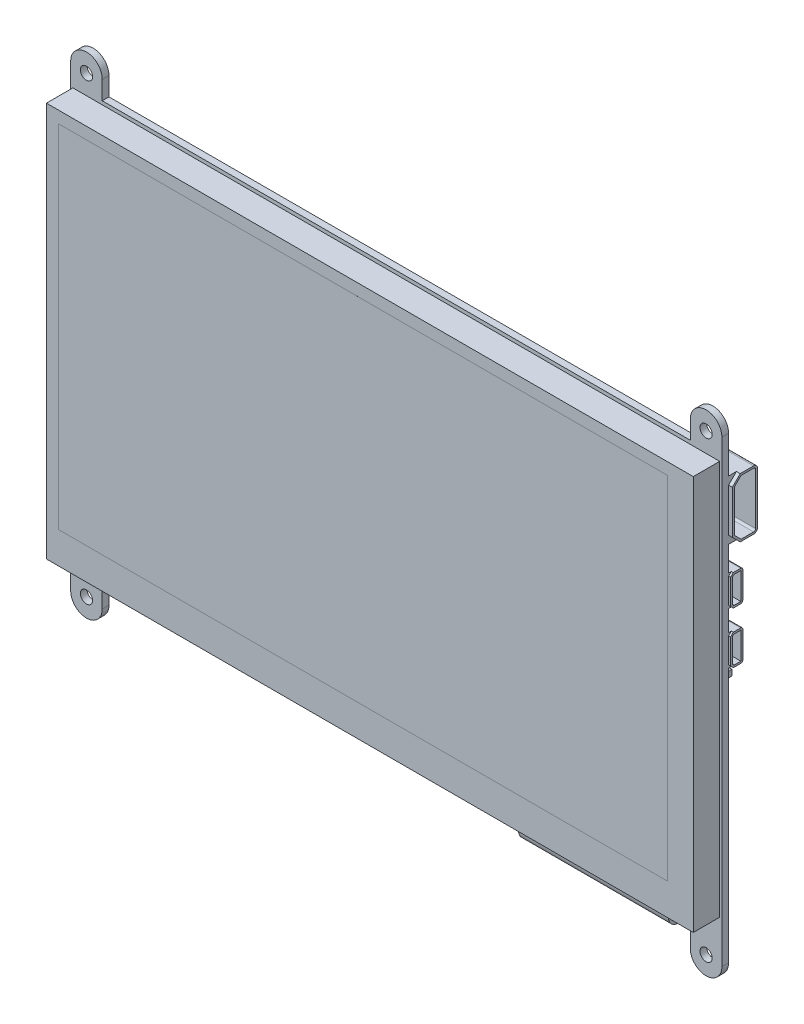
SolidWorks part; units mm, degrees
ref_plane "Přední rovina" through (0, 0, 0) normal (0, 0, 1) x (1, 0, 0)
ref_plane "Horní rovina" through (0, 0, 0) normal (0, 1, 0) x (1, 0, 0)
ref_plane "Pravá rovina" through (0, 0, 0) normal (1, 0, 0) x (0, 0, -1)
sketch "Skica1" plane through (0, 0, 0) normal (0, 0, 1) x (1, 0, 0)
  line L1 (-82, -50.05) -> (82, -50.05)
  line L2 (-82, -50.05) -> (-82, 50.05)
  line L3 (-82, 50.05) -> (82, 50.05)
  line L4 (82, -50.05) -> (82, 50.05)
  line L5 (-82, -50.05) -> (82, 50.05) construction
  line L6 (-82, 50.05) -> (82, -50.05) construction
  line L7 (-82.55, -55.95) -> (82.55, -55.95)
  line L8 (-82.55, -55.95) -> (-82.55, 50.95)
  line L9 (-82.55, 50.95) -> (82.55, 50.95)
  line L10 (82.55, -55.95) -> (82.55, 50.95)
  line L11 (-82.55, -55.95) -> (82.55, 50.95) construction
  line L12 (-82.55, 50.95) -> (82.55, -55.95) construction
  point P0 (0, 0)
  point P6 (0, -2.5)
  dimension "D1" = 100.1
  dimension "D2" = 164
  dimension "D3" = 106.9
  dimension "D4" = 0.55
  dimension "D5" = 0.55
  dimension "D6" = 0.9
extrude "Přidat vysunutím1" add sketch "Skica1" along normal blind 6.7 contours L1 L4 L3 L2 region at (0, 0, 0)
extrude "Přidat vysunutím2" add sketch "Skica1<3>" against normal blind 1.7 contours L10 L9 L8 L7
sketch "Skica1<3>" plane through (0, 0, 0) normal (0, 0, 1) x (1, 0, 0) same geometry as "Skica1"
sketch "Skica2" plane through (0, 0, -1.7) normal (0, 0, -1) x (-1, 0, 0)
  line L0 (0, 0) -> (0, -91.8363) construction
  line L1 (-82.55, -2.5) -> (0, -2.5) construction
  line L2 (-82.55, -55.95) -> (-82.55, 50.95) construction
  line L3 (-78.55, 50.95) -> (-78.55, 55.65) construction
  line L4 (82.55, 50.95) -> (-82.55, 50.95) construction
  line L5 (-82.55, 50.95) -> (-82.55, 55.65)
  line L6 (-74.55, 50.95) -> (-74.55, 55.65)
  line L7 (-78.55, -55.95) -> (-78.55, -60.65) construction
  line L8 (-82.55, -55.95) -> (-82.55, -60.65)
  line L9 (-74.55, -55.95) -> (-74.55, -60.65)
  line L10 (-78.55, -55.95) -> (-78.55, -60.65) construction
  line L11 (-82.55, -55.95) -> (-82.55, -60.65)
  line L12 (-74.55, -55.95) -> (-74.55, -60.65)
  line L13 (-78.55, 50.95) -> (-78.55, 55.65) construction
  line L14 (-82.55, 50.95) -> (-82.55, 55.65)
  line L15 (-74.55, 50.95) -> (-74.55, 55.65)
  line L16 (78.55, 50.95) -> (78.55, 55.65) construction
  line L17 (82.55, 50.95) -> (82.55, 55.65)
  line L18 (74.55, 50.95) -> (74.55, 55.65)
  line L19 (78.55, -55.95) -> (78.55, -60.65) construction
  line L20 (82.55, -55.95) -> (82.55, -60.65)
  line L21 (74.55, -55.95) -> (74.55, -60.65)
  line L22 (78.55, -55.95) -> (78.55, -60.65) construction
  line L23 (82.55, -55.95) -> (82.55, -60.65)
  line L24 (74.55, -55.95) -> (74.55, -60.65)
  line L25 (78.55, 50.95) -> (78.55, 55.65) construction
  line L26 (82.55, 50.95) -> (82.55, 55.65)
  line L27 (74.55, 50.95) -> (74.55, 55.65)
  arc A0 (-82.55, 50.95) -> (-74.55, 50.95) centre (-78.55, 50.95) ccw
  arc A1 (-74.55, 55.65) -> (-82.55, 55.65) centre (-78.55, 55.65) ccw
  circle A2 centre (-78.55, 55) radius 1.55
  circle A3 centre (-78.55, -60) radius 1.55
  arc A4 (-82.55, -55.95) -> (-74.55, -55.95) centre (-78.55, -55.95) cw
  arc A5 (-74.55, -60.65) -> (-82.55, -60.65) centre (-78.55, -60.65) cw
  arc A6 (-82.55, -55.95) -> (-74.55, -55.95) centre (-78.55, -55.95) cw
  arc A7 (-74.55, -60.65) -> (-82.55, -60.65) centre (-78.55, -60.65) cw
  arc A8 (-82.55, 50.95) -> (-74.55, 50.95) centre (-78.55, 50.95) ccw
  arc A9 (-74.55, 55.65) -> (-82.55, 55.65) centre (-78.55, 55.65) ccw
  circle A10 centre (-78.55, 55) radius 1.55
  circle A11 centre (-78.55, -60) radius 1.55
  circle A12 centre (78.55, -60) radius 1.55
  circle A13 centre (78.55, 55) radius 1.55
  circle A14 centre (78.55, -60) radius 1.55
  circle A15 centre (78.55, 55) radius 1.55
  arc A16 (82.55, 50.95) -> (74.55, 50.95) centre (78.55, 50.95) cw
  arc A17 (74.55, 55.65) -> (82.55, 55.65) centre (78.55, 55.65) cw
  arc A18 (82.55, -55.95) -> (74.55, -55.95) centre (78.55, -55.95) ccw
  arc A19 (74.55, -60.65) -> (82.55, -60.65) centre (78.55, -60.65) ccw
  arc A20 (82.55, -55.95) -> (74.55, -55.95) centre (78.55, -55.95) ccw
  arc A21 (74.55, -60.65) -> (82.55, -60.65) centre (78.55, -60.65) ccw
  arc A22 (82.55, 50.95) -> (74.55, 50.95) centre (78.55, 50.95) cw
  arc A23 (74.55, 55.65) -> (82.55, 55.65) centre (78.55, 55.65) cw
  point P11 (-78.55, 53.3)
  point P18 (-78.55, 59.65)
  point P23 (-78.55, -58.3)
  point P30 (-78.55, -58.3)
  point P37 (-78.55, 53.3)
  point P52 (78.55, 53.3)
  point P59 (78.55, -58.3)
  point P66 (78.55, -58.3)
  point P73 (78.55, 53.3)
  line M7 (-82.55, -55.95) -> (82.55, -55.95)
  line M9 (82.55, 50.95) -> (-82.55, 50.95)
  dimension "D1" = 8.7
  dimension "D2" = 3.1
  dimension "D4" = 3.1
  dimension "D3" = 8
extrude "Přidat vysunutím3" add sketch "Skica2" against normal up to surface (1.7 mm away) contours A5 L9 L8 A3 M7 | L21 A19 L20 A12 M7 | A17 L18 L17 A13 M9 | L6 A1 L5 A2 M9 region at (-74.6682, 53.3, -1.7) region at (82.4318, 53.3, -1.7) region at (78.55, -56.0682, -1.7) region at (-78.55, -56.0682, -1.7) up to face at (0, -2.5, 0)
sketch "Skica3" plane through (0, 0, 6.7) normal (0, 0, 1) x (1, 0, 0)
  line L0 (-82, 50.05) -> (82, 50.05) construction
  line L1 (75.5, 47.05) -> (-79, 47.05)
  line L2 (75.5, 47.05) -> (75.5, -42.05)
  line L3 (75.5, -42.05) -> (-79, -42.05)
  line L4 (-79, 47.05) -> (-79, -42.05)
  line L5 (75.5, 47.05) -> (-79, -42.05) construction
  line L6 (75.5, -42.05) -> (-79, 47.05) construction
  line L7 (-82, -50.05) -> (82, -50.05) construction
  line L8 (-82, -50.05) -> (-82, 50.05) construction
  line L9 (82, -50.05) -> (82, 50.05) construction
  point P0 (-1.75, 2.5)
  dimension "D1" = 3
  dimension "D2" = 8
  dimension "D3" = 3
  dimension "D4" = 6.5
extrude "Odebrat vysunutím1" cut sketch "Skica3" against normal blind 1.5
extrude "Přidat vysunutím4" add sketch "Skica3<2>" against normal blind 1.5 separate body
sketch "Skica3<2>" plane through (0, 0, 6.7) normal (0, 0, 1) x (1, 0, 0) same geometry as "Skica3"
sketch "Skica4" plane through (0, 0, 0) normal (0, 0, 1) x (1, 0, 0)
  line L0 (-82, -50.05) -> (82, -50.05) construction
  line L1 (75.3, -50.05) -> (37.3, -50.05)
  line L2 (75.3, -50.05) -> (75.3, -52.8)
  line L3 (75.3, -52.8) -> (37.3, -52.8)
  line L4 (37.3, -50.05) -> (37.3, -52.8)
  dimension "D1" = 38
  dimension "D2" = 2.75
  dimension "D3" = 6.7
extrude "Přidat vysunutím5" add sketch "Skica4" along normal blind 6.3
fillet "Zaoblit1" radius 2.5 1 edges at (56.3, -52.8, 6.3)
sketch "Skica5" plane through (0, 0, 0) normal (0, 0, 1) x (1, 0, 0)
  line L0 (-82, -50.05) -> (37.3, -50.05) construction
  line L1 (-14.55, -50.05) -> (13.95, -50.05)
  line L2 (-14.55, -50.05) -> (-14.55, -50.95)
  line L3 (-14.55, -50.95) -> (13.95, -50.95)
  line L4 (13.95, -50.05) -> (13.95, -50.95)
  line L5 (82.55, -60.65) -> (82.55, 55.65) construction
  dimension "D1" = 28.5
  dimension "D2" = 0.9
  dimension "D3" = 68.6
extrude "Přidat vysunutím6" add sketch "Skica5" along normal blind 4.3
fillet "Zaoblit2" radius 3 1 edges at (-0.3, -50.95, 4.3)
sketch "Skica6" plane through (0, 0, -1.7) normal (0, 0, -1) x (-1, 0, 0)
  line L0 (74.55, 50.95) -> (-74.55, 50.95) construction
  line L1 (-21.65, 11.45) -> (-1.75, 11.45)
  line L2 (-21.65, 11.45) -> (-21.65, 25.25)
  line L3 (-21.65, 25.25) -> (-1.75, 25.25)
  line L4 (-1.75, 11.45) -> (-1.75, 25.25)
  line L5 (-21.65, 11.45) -> (-1.75, 25.25) construction
  line L6 (-21.65, 25.25) -> (-1.75, 11.45) construction
  line L7 (-23.55, 11.95) -> (0.15, 11.95)
  line L8 (-23.55, 11.95) -> (-23.55, 24.75)
  line L9 (-23.55, 24.75) -> (0.15, 24.75)
  line L10 (0.15, 11.95) -> (0.15, 24.75)
  line L11 (-23.55, 11.95) -> (0.15, 24.75) construction
  line L12 (-23.55, 24.75) -> (0.15, 11.95) construction
  line L13 (-21.1, 9.45) -> (-2.3, 9.45)
  line L14 (-21.1, 9.45) -> (-21.1, 27.25)
  line L15 (-21.1, 27.25) -> (-2.3, 27.25)
  line L16 (-2.3, 9.45) -> (-2.3, 27.25)
  line L17 (-21.1, 9.45) -> (-2.3, 27.25) construction
  line L18 (-21.1, 27.25) -> (-2.3, 9.45) construction
  line L19 (-82.55, -60.65) -> (-82.55, 55.65) construction
  line L20 (82.55, -60.65) -> (82.55, 55.65) construction
  line L21 (32.45, 6.95) -> (66.45, 6.95)
  line L22 (32.45, 6.95) -> (32.45, 29.35)
  line L23 (32.45, 29.35) -> (66.45, 29.35)
  line L24 (66.45, 6.95) -> (66.45, 29.35)
  line L25 (26.55, 23.25) -> (18.25, 23.25)
  line L26 (26.55, 23.25) -> (26.55, 6.85)
  line L27 (26.55, 6.85) -> (18.25, 6.85)
  line L28 (18.25, 23.25) -> (18.25, 6.85)
  line L29 (18.25, 23.25) -> (13.85, 23.25)
  line L30 (18.25, 23.25) -> (18.25, 12.25)
  line L31 (18.25, 12.25) -> (13.85, 12.25)
  line L32 (13.85, 23.25) -> (13.85, 12.25)
  line L33 (2.75, 12.85) -> (5.65, 12.85)
  line L34 (2.75, 12.85) -> (2.75, 30.05)
  line L35 (2.75, 30.05) -> (5.65, 30.05)
  line L36 (5.65, 12.85) -> (5.65, 30.05)
  line L37 (5.65, 30.05) -> (9.75, 30.05)
  line L38 (5.65, 30.05) -> (5.65, 25.75)
  line L39 (5.65, 25.75) -> (9.75, 25.75)
  line L40 (9.75, 30.05) -> (9.75, 25.75)
  point P0 (-11.7, 18.35)
  point P5 (-11.7, 18.35)
  point P10 (-11.7, 18.35)
  point P40 (9.75, 27.9)
  dimension "D1" = 19.9
  dimension "D2" = 13.8
  dimension "D3" = 12.8
  dimension "D4" = 18.8
  dimension "D5" = 23.7
  dimension "D6" = 17.8
  dimension "D7" = 25.7
  dimension "D8" = 60.9
  dimension "D9" = 34
  dimension "D10" = 22.4
  dimension "D11" = 16.1
  dimension "D12" = 21.6
  dimension "D13" = 8.3
  dimension "D14" = 12.7
  dimension "D15" = 16.4
  dimension "D16" = 11
  dimension "D17" = 27.7
  dimension "D18" = 56
  dimension "D19" = 17.2
  dimension "D20" = 7
  dimension "D21" = 4.3
  dimension "D22" = 20.9
  dimension "D23" = 72.8
  dimension "D24" = 2.9
extrude "Přidat vysunutím7" add sketch "Skica6" along normal blind 2.4 contours L21 L24 L23 L22 region at (-49.45, 18.15, -1.7)
extrude "Přidat vysunutím8" add sketch "Skica6<3>" along normal blind 1.8 contours L25 L28 L27 L26 region at (-22.4, 15.05, -1.7)
sketch "Skica6<3>" plane through (0, 0, -1.7) normal (0, 0, -1) x (-1, 0, 0) same geometry as "Skica6"
extrude "Přidat vysunutím9" add sketch "Skica6<4>" along normal blind 1 contours L29 L32 L31 L28 region at (-16.05, 17.75, -1.7)
sketch "Skica6<4>" plane through (0, 0, -1.7) normal (0, 0, -1) x (-1, 0, 0) same geometry as "Skica6"
extrude "Přidat vysunutím10" add sketch "Skica6<5>" along normal blind 1 contours L33 L36 L35 L34 | L37 L40 L39 L38 region at (-4.2, 21.45, -1.7)
sketch "Skica6<5>" plane through (0, 0, -1.7) normal (0, 0, -1) x (-1, 0, 0) same geometry as "Skica6"
extrude "Přidat vysunutím11" add sketch "Skica6<6>" along normal blind 1.45 contours L2 L3 L4 L1
sketch "Skica6<6>" plane through (0, 0, -1.7) normal (0, 0, -1) x (-1, 0, 0) same geometry as "Skica6"
extrude "Přidat vysunutím12" add sketch "Skica6<7>" along normal blind 0.8 contours L7 L10 L9 L4 | L15 L16 L13 L14 | L8 L9 L10 L7 region at (0.8, 18.35, -1.7)
sketch "Skica6<7>" plane through (0, 0, -1.7) normal (0, 0, -1) x (-1, 0, 0) same geometry as "Skica6"
chamfer "Zkosení1" distance 0.8 angle 45 4 edges at (11.7, 27.25, -2.5) (23.55, 18.35, -2.5) (-0.15, 18.35, -2.5) (11.7, 9.45, -2.5)
sketch "Skica7" plane through (0, 0, -1.7) normal (0, 0, -1) x (-1, 0, 0)
  line L0 (74.55, -55.95) -> (-74.55, -55.95) construction
  line L1 (-35.45, -32.65) -> (-28.65, -32.65)
  line L2 (-35.45, -32.65) -> (-35.45, -25.85)
  line L3 (-35.45, -25.85) -> (-28.65, -25.85)
  line L4 (-28.65, -32.65) -> (-28.65, -25.85)
  line L5 (-35.45, -32.65) -> (-28.65, -25.85) construction
  line L6 (-35.45, -25.85) -> (-28.65, -32.65) construction
  line L7 (-34.9, -34.25) -> (-29.2, -34.25)
  line L8 (-34.9, -34.25) -> (-34.9, -24.25)
  line L9 (-34.9, -24.25) -> (-29.2, -24.25)
  line L10 (-29.2, -34.25) -> (-29.2, -24.25)
  line L11 (-34.9, -34.25) -> (-29.2, -24.25) construction
  line L12 (-34.9, -24.25) -> (-29.2, -34.25) construction
  line L13 (-37.05, -32.1) -> (-27.05, -32.1)
  line L14 (-37.05, -32.1) -> (-37.05, -26.4)
  line L15 (-37.05, -26.4) -> (-27.05, -26.4)
  line L16 (-27.05, -32.1) -> (-27.05, -26.4)
  line L17 (-37.05, -32.1) -> (-27.05, -26.4) construction
  line L18 (-37.05, -26.4) -> (-27.05, -32.1) construction
  line L19 (-82.55, -60.65) -> (-82.55, 55.65) construction
  line L20 (-45.9, -24.6) -> (-45.9, -31) construction
  line L21 (-24.15, -32.45) -> (-21.85, -32.45)
  line L22 (-24.15, -32.45) -> (-24.15, -24.65)
  line L23 (-24.15, -24.65) -> (-21.85, -24.65)
  line L24 (-21.85, -32.45) -> (-21.85, -24.65)
  line L25 (-34.05, -21.85) -> (-29.55, -21.85)
  line L26 (-34.05, -21.85) -> (-34.05, -19.35)
  line L27 (-34.05, -19.35) -> (-29.55, -19.35)
  line L28 (-29.55, -21.85) -> (-29.55, -19.35)
  line L29 (-42.15, -35.15) -> (-40.5, -35.15)
  line L30 (-42.15, -35.15) -> (-42.15, -24.85)
  line L31 (-42.15, -24.85) -> (-40.5, -24.85)
  line L32 (-40.5, -35.15) -> (-40.5, -24.85)
  line L33 (-40.5, -35.15) -> (-38.85, -35.15)
  line L34 (-40.5, -35.15) -> (-40.5, -29.25)
  line L35 (-40.5, -29.25) -> (-38.85, -29.25)
  line L36 (-38.85, -35.15) -> (-38.85, -29.25)
  line L37 (-44.15, -24.6) -> (-44.15, -31)
  line L38 (-47.65, -24.6) -> (-47.65, -31)
  line L39 (-45.9, -31) -> (-45.9, -24.6) construction
  line L40 (-48.15, -31) -> (-48.15, -24.6)
  line L41 (-43.65, -31) -> (-43.65, -24.6)
  line L43 (-29.55, -37.45) -> (-27.55, -37.45)
  line L44 (-29.55, -37.45) -> (-29.55, -36.15)
  line L45 (-29.55, -36.15) -> (-27.55, -36.15)
  line L46 (-27.55, -37.45) -> (-27.55, -36.15)
  arc A0 (-44.15, -24.6) -> (-47.65, -24.6) centre (-45.9, -24.6) ccw
  arc A1 (-47.65, -31) -> (-44.15, -31) centre (-45.9, -31) ccw
  arc A2 (-48.15, -31) -> (-43.65, -31) centre (-45.9, -31) ccw
  arc A3 (-43.65, -24.6) -> (-48.15, -24.6) centre (-45.9, -24.6) ccw
  point P0 (-32.05, -29.25)
  point P5 (-32.05, -29.25)
  point P10 (-32.05, -29.25)
  point P36 (-45.9, -27.8)
  point P41 (-45.9, -27.8)
  point P48 (-45.9, -32.75)
  point P49 (-47.65, -27.8)
  dimension "D10" = 23.2
  dimension "D1" = 6.8
  dimension "D2" = 5.7
  dimension "D3" = 10
  dimension "D4" = 23.3
  dimension "D5" = 47.1
  dimension "D6" = 4.5
  dimension "D7" = 3.5
  dimension "D8" = 9.9
  dimension "D9" = 34.9
  dimension "D11" = 3.3
  dimension "D12" = 10.3
  dimension "D13" = 5.9
  dimension "D14" = 20.8
  dimension "D15" = 40.4
  dimension "D16" = 2.3
  dimension "D17" = 7.8
  dimension "D18" = 23.5
  dimension "D19" = 4.5
  dimension "D20" = 4.5
  dimension "D21" = 2.5
  dimension "D22" = 4
  dimension "D23" = 48.5
  dimension "D24" = 2
  dimension "D25" = 1.3
  dimension "D26" = 18.5
  dimension "D27" = 53
extrude "Přidat vysunutím13" add sketch "Skica7" along normal blind 1.5 contours L1 L4 L3 L2
extrude "Přidat vysunutím14" add sketch "Skica7<3>" along normal blind 0.8 contours L16 L15 L14 L13 | L9 L10 L7 L8
sketch "Skica7<3>" plane through (0, 0, -1.7) normal (0, 0, -1) x (-1, 0, 0) same geometry as "Skica7"
extrude "Přidat vysunutím15" add sketch "Skica7<4>" along normal blind 0.7 contours L41 A3 L40 A2
sketch "Skica7<4>" plane through (0, 0, -1.7) normal (0, 0, -1) x (-1, 0, 0) same geometry as "Skica7"
extrude "Přidat vysunutím16" add sketch "Skica7<5>" along normal blind 4.2 contours L37 A1 L38 A0
sketch "Skica7<5>" plane through (0, 0, -1.7) normal (0, 0, -1) x (-1, 0, 0) same geometry as "Skica7"
extrude "Přidat vysunutím17" add sketch "Skica7<6>" along normal blind 0.8 contours L33 L36 L35 L34 | L29 L30 L31 L32 | L24 L23 L22 L21 | L43 L46 L45 L44 | L25 L28 L27 L26
sketch "Skica7<6>" plane through (0, 0, -1.7) normal (0, 0, -1) x (-1, 0, 0) same geometry as "Skica7"
chamfer "Zkosení2" distance 0.8 angle 45 4 edges at (32.05, -24.25, -2.5) (37.05, -29.25, -2.5) (27.05, -29.25, -2.5) (32.05, -34.25, -2.5)
sketch "Skica8" plane through (0, 0, -1.7) normal (0, 0, -1) x (-1, 0, 0)
  line L0 (74.55, -55.95) -> (-74.55, -55.95) construction
  line L1 (-17.15, -36.45) -> (20.55, -36.45)
  line L2 (-17.15, -36.45) -> (-17.15, -31.45)
  line L3 (-17.15, -31.45) -> (20.55, -31.45)
  line L4 (20.55, -36.45) -> (20.55, -31.45)
  line L5 (82.55, -60.65) -> (82.55, 55.65) construction
  dimension "D1" = 5
  dimension "D2" = 37.7
  dimension "D3" = 19.5
  dimension "D4" = 62
extrude "Odebrat vysunutím2" cut sketch "Skica8" against normal blind 1.6
sketch "Skica9" plane through (0, 0, -1.7) normal (0, 0, -1) x (-1, 0, 0)
  line L0 (1.1, -10.85) -> (1.1, -1.0919) construction
  line L1 (13.9, -12.85) -> (-11.7, -12.85)
  line L2 (13.9, -12.85) -> (13.9, -8.85)
  line L3 (13.9, -8.85) -> (-11.7, -8.85)
  line L4 (-11.7, -12.85) -> (-11.7, -8.85)
  line L5 (13.9, -12.85) -> (-11.7, -8.85) construction
  line L6 (13.9, -8.85) -> (-11.7, -12.85) construction
  line L7 (-14.05, -13.35) -> (-11.7, -13.35)
  line L8 (-14.05, -13.35) -> (-14.05, -8.35)
  line L9 (-14.05, -8.35) -> (-11.7, -8.35)
  line L10 (-11.7, -13.35) -> (-11.7, -8.35)
  line L11 (-14.05, -13.35) -> (-11.7, -8.35) construction
  line L12 (-14.05, -8.35) -> (-11.7, -13.35) construction
  line L13 (16.25, -8.35) -> (13.9, -13.35) construction
  line L14 (13.9, -12.85) -> (13.9, -8.85)
  line L15 (16.25, -13.35) -> (13.9, -8.35) construction
  line L16 (13.9, -13.35) -> (13.9, -8.35)
  line L17 (16.25, -13.35) -> (13.9, -13.35)
  line L18 (16.25, -8.35) -> (13.9, -8.35)
  line L19 (16.25, -13.35) -> (16.25, -8.35)
  line L20 (82.55, -60.65) -> (82.55, 55.65) construction
  line L21 (74.55, -55.95) -> (-74.55, -55.95) construction
  point P0 (1.1, -10.85)
  point P5 (-12.875, -10.85)
  point P10 (15.075, -10.85)
  dimension "D1" = 4
  dimension "D2" = 30.3
  dimension "D3" = 25.6
  dimension "D4" = 5
  dimension "D5" = 66.3
  dimension "D6" = 43.1
extrude "Přidat vysunutím18" add sketch "Skica9" along normal blind 2 contours L4 L1 L2 L3 region at (-1.1, -10.85, -1.7)
extrude "Přidat vysunutím19" add sketch "Skica9<3>" along normal blind 2.1 contours L8 L9 L10 L7 | L19 L18 L16 L17
sketch "Skica9<3>" plane through (0, 0, -1.7) normal (0, 0, -1) x (-1, 0, 0) same geometry as "Skica9"
chamfer "Zkosení3" distance 0.5 angle 45 1 edges at (-1.1, -8.85, -1.7)
sketch "Skica10" plane through (0, 0, -1.7) normal (0, 0, -1) x (-1, 0, 0)
  line L0 (13.9, -12.85) -> (-11.7, -12.85) construction
  line L1 (-11.7, -12.85) -> (13.9, -12.85)
  line L2 (-11.7, -12.85) -> (-11.7, -33.85)
  line L3 (-11.7, -33.85) -> (13.9, -33.85)
  line L4 (13.9, -12.85) -> (13.9, -33.85)
  line L5 (-14.6, -29.35) -> (-11.7, -24.85)
  line L6 (-11.7, -33.85) -> (-14.6, -33.85)
  line L7 (-11.7, -33.85) -> (-11.7, -29.35)
  line L8 (-11.7, -29.35) -> (-14.6, -29.35)
  line L9 (-14.6, -33.85) -> (-14.6, -29.35)
  dimension "D1" = 21
  dimension "D2" = 28.5
  dimension "D3" = 16.5
  dimension "D4" = 4.5
extrude "Přidat vysunutím20" add sketch "Skica10" along direction (0, 0, 1) on the side against the normal up to surface (1.6 mm away) and the other way blind 1.25 contours L4 L1 L2 L3 | L9 L6 L2 L8 | L8 L2 L5 region at (-1.1, -23.35, -1.7) region at (12.6667, -27.85, -1.7) region at (13.15, -31.6, -1.7) up to face at (-1.7, -33.95, -0.1)
fillet "Zaoblit3" radius 3 1 edges at (0.35, -33.85, -2.95)
sketch "Skica11" plane through (0, 0, -1.7) normal (0, 0, -1) x (-1, 0, 0)
  line L0 (-36.95, -7.85) -> (-36.95, 5.6861) construction
  line L5 (74.55, -55.95) -> (-74.55, -55.95) construction
  line L6 (-82.55, -60.65) -> (-82.55, 55.65) construction
  line L7 (-40.15, -9.55) -> (-33.75, -9.55)
  line L8 (-40.15, -9.55) -> (-40.15, -6.15)
  line L9 (-40.15, -6.15) -> (-33.75, -6.15)
  line L10 (-33.75, -9.55) -> (-33.75, -6.15)
  line L11 (-40.15, -9.55) -> (-33.75, -6.15) construction
  line L12 (-40.15, -6.15) -> (-33.75, -9.55) construction
  line L13 (-38.45, -3.65) -> (-35.45, -3.65)
  line L14 (-38.45, -3.65) -> (-38.45, -6.15)
  line L15 (-38.45, -6.15) -> (-35.45, -6.15)
  line L16 (-35.45, -3.65) -> (-35.45, -6.15)
  line L17 (-38.45, -3.65) -> (-35.45, -6.15) construction
  line L18 (-38.45, -6.15) -> (-35.45, -3.65) construction
  line L19 (-36.575, -11.65) -> (-37.325, -11.65)
  line L20 (-36.575, -11.65) -> (-36.575, -9.55)
  line L21 (-36.575, -9.55) -> (-37.325, -9.55)
  line L22 (-37.325, -11.65) -> (-37.325, -9.55)
  line L23 (-36.575, -11.65) -> (-37.325, -9.55) construction
  line L24 (-36.575, -9.55) -> (-37.325, -11.65) construction
  line L25 (-39.575, -11.65) -> (-38.825, -11.65)
  line L26 (-39.575, -11.65) -> (-39.575, -9.55)
  line L27 (-39.575, -9.55) -> (-38.825, -9.55)
  line L28 (-38.825, -11.65) -> (-38.825, -9.55)
  line L29 (-39.575, -11.65) -> (-38.825, -9.55) construction
  line L30 (-39.575, -9.55) -> (-38.825, -11.65) construction
  line L31 (-34.325, -9.55) -> (-35.075, -11.65) construction
  line L32 (-34.325, -11.65) -> (-35.075, -9.55) construction
  line L33 (-35.075, -11.65) -> (-35.075, -9.55)
  line L34 (-34.325, -11.65) -> (-34.325, -9.55)
  line L35 (-34.325, -11.65) -> (-35.075, -11.65)
  line L36 (-40.15, 2.45) -> (-33.75, 2.45)
  line L37 (-40.15, 2.45) -> (-40.15, 5.85)
  line L38 (-40.15, 5.85) -> (-33.75, 5.85)
  line L39 (-33.75, 2.45) -> (-33.75, 5.85)
  line L40 (-38.45, 8.35) -> (-35.45, 8.35)
  line L41 (-38.45, 8.35) -> (-38.45, 5.85)
  line L42 (-38.45, 5.85) -> (-35.45, 5.85)
  line L43 (-35.45, 8.35) -> (-35.45, 5.85)
  line L44 (-36.575, 0.35) -> (-37.325, 0.35)
  line L45 (-36.575, 0.35) -> (-36.575, 2.45)
  line L46 (-36.575, 2.45) -> (-37.325, 2.45)
  line L47 (-37.325, 0.35) -> (-37.325, 2.45)
  line L48 (-39.575, 0.35) -> (-38.825, 0.35)
  line L49 (-39.575, 0.35) -> (-39.575, 2.45)
  line L50 (-39.575, 2.45) -> (-38.825, 2.45)
  line L51 (-38.825, 0.35) -> (-38.825, 2.45)
  line L52 (-35.075, 0.35) -> (-35.075, 2.45)
  line L53 (-34.325, 0.35) -> (-34.325, 2.45)
  line L54 (-34.325, 0.35) -> (-35.075, 0.35)
  line L55 (-36.95, 4.15) -> (-36.95, 17.6861) construction
  line L56 (-40.15, 2.45) -> (-33.75, 5.85) construction
  line L57 (-40.15, 5.85) -> (-33.75, 2.45) construction
  line L58 (-38.45, 8.35) -> (-35.45, 5.85) construction
  line L59 (-38.45, 5.85) -> (-35.45, 8.35) construction
  line L60 (-36.575, 0.35) -> (-37.325, 2.45) construction
  line L61 (-36.575, 2.45) -> (-37.325, 0.35) construction
  line L62 (-39.575, 0.35) -> (-38.825, 2.45) construction
  line L63 (-39.575, 2.45) -> (-38.825, 0.35) construction
  line L64 (-34.325, 2.45) -> (-35.075, 0.35) construction
  line L65 (-34.325, 0.35) -> (-35.075, 2.45) construction
  point P5 (-36.95, -7.85)
  point P10 (-36.95, -4.9)
  point P15 (-36.95, -10.6)
  point P20 (-39.2, -10.6)
  point P32 (-34.7, -10.6)
  point P34 (-36.95, 4.15)
  point P39 (-36.95, 7.1)
  point P44 (-36.95, 1.4)
  point P49 (-39.2, 1.4)
  point P58 (-34.7, 1.4)
  dimension "D1" = 6.4
  dimension "D2" = 3.4
  dimension "D3" = 0.75
  dimension "D4" = 3
  dimension "D5" = 3
  dimension "D6" = 2.1
  dimension "D7" = 2.5
  dimension "D8" = 49.8
  dimension "D9" = 48.8
  dimension "D10" = 2
extrude "Přidat vysunutím21" add sketch "Skica11" along normal blind 1.9 contours L7 L10 L9 L8 | L36 L39 L38 L37 region at (36.95, -7.85, -1.7) region at (36.95, 4.15, -1.7)
extrude "Přidat vysunutím23" add sketch "Skica11<3>" along normal blind 0.8 contours L35 L34 L7 L33 | L43 L40 L41 L38 | L48 L51 L36 L49 | L47 L44 L45 L36 | L54 L53 L36 L52 | L14 L15 L16 L13 | L26 L27 L28 L25 | L22 L21 L20 L19 region at (34.7, -10.6, -1.7) region at (39.2, 1.4, -1.7) region at (36.95, 7.1, -1.7) region at (36.95, 1.4, -1.7) region at (34.7, 1.4, -1.7)
sketch "Skica11<3>" plane through (0, 0, -1.7) normal (0, 0, -1) x (-1, 0, 0) same geometry as "Skica11"
chamfer "Zkosení4" distance 0.8 angle 45 8 edges at (39.2, 0.35, -2.5) (34.7, 0.35, -2.5) (36.95, 0.35, -2.5) (36.95, 8.35, -2.5) (36.95, -3.65, -2.5) (34.7, -11.65, -2.5) (36.95, -11.65, -2.5) (39.2, -11.65, -2.5)
sketch "Skica12" plane through (0, 0, -1.7) normal (0, 0, -1) x (-1, 0, 0)
  line L0 (74.55, 50.95) -> (-74.55, 50.95) construction
  line L1 (-30.35, -11.65) -> (-27.85, -11.65)
  line L2 (-30.35, -11.65) -> (-30.35, -4.15)
  line L3 (-30.35, -4.15) -> (-27.85, -4.15)
  line L4 (-27.85, -11.65) -> (-27.85, -4.15)
  line L5 (-30.35, 1.75) -> (-27.85, 1.75)
  line L6 (-30.35, 1.75) -> (-30.35, 4.95)
  line L7 (-30.35, 4.95) -> (-27.85, 4.95)
  line L8 (-27.85, 1.75) -> (-27.85, 4.95)
  line L9 (-30.35, 10.15) -> (-27.85, 10.15)
  line L10 (-30.35, 10.15) -> (-30.35, 14.65)
  line L11 (-30.35, 14.65) -> (-27.85, 14.65)
  line L12 (-27.85, 10.15) -> (-27.85, 14.65)
  line L13 (-30.35, 18.65) -> (-27.85, 18.65)
  line L14 (-30.35, 18.65) -> (-30.35, 19.65)
  line L15 (-30.35, 19.65) -> (-27.85, 19.65)
  line L16 (-27.85, 18.65) -> (-27.85, 19.65)
  line L17 (-16.55, -2.75) -> (-5.55, -2.75)
  line L18 (-16.55, -2.75) -> (-16.55, -0.25)
  line L19 (-16.55, -0.25) -> (-5.55, -0.25)
  line L20 (-5.55, -2.75) -> (-5.55, -0.25)
  line L21 (-14.25, 30.25) -> (-11.45, 30.25)
  line L22 (-14.25, 30.25) -> (-14.25, 32.75)
  line L23 (-14.25, 32.75) -> (-11.45, 32.75)
  line L24 (-11.45, 30.25) -> (-11.45, 32.75)
  line L25 (-1.95, 30.25) -> (0.85, 30.25)
  line L26 (-1.95, 30.25) -> (-1.95, 32.75)
  line L27 (-1.95, 32.75) -> (0.85, 32.75)
  line L28 (0.85, 30.25) -> (0.85, 32.75)
  line L29 (-18.65, 4.05) -> (-17.65, 4.05)
  line L30 (-18.65, 4.05) -> (-18.65, 6.55)
  line L31 (-18.65, 6.55) -> (-17.65, 6.55)
  line L32 (-17.65, 4.05) -> (-17.65, 6.55)
  line L33 (-12.15, 4.05) -> (-11.15, 4.05)
  line L34 (-12.15, 4.05) -> (-12.15, 6.55)
  line L35 (-12.15, 6.55) -> (-11.15, 6.55)
  line L36 (-11.15, 4.05) -> (-11.15, 6.55)
  line L37 (-82.55, -60.65) -> (-82.55, 55.65) construction
  dimension "D1" = 11
  dimension "D2" = 2.5
  dimension "D3" = 7.5
  dimension "D4" = 3.2
  dimension "D5" = 4.5
  dimension "D6" = 1
  dimension "D7" = 31.3
  dimension "D8" = 31.3
  dimension "D9" = 5.9
  dimension "D10" = 5.2
  dimension "D11" = 52.2
  dimension "D12" = 18.2
  dimension "D13" = 2.8
  dimension "D14" = 9.5
  dimension "D15" = 68.3
  dimension "D16" = 5.5
  dimension "D17" = 46.9
  dimension "D18" = 63.9
  dimension "D19" = 66
  dimension "D20" = 51.2
extrude "Přidat vysunutím24" add sketch "Skica12" along normal blind 1.6
sketch "Skica14" plane through (0, 0, -1.7) normal (0, 0, -1) x (-1, 0, 0)
  line L0 (-5.55, -2.75) -> (-5.55, -0.25) construction
  line L1 (8.55, -2.75) -> (10.95, -2.75)
  line L2 (8.55, -2.75) -> (8.55, -0.05)
  line L3 (8.55, -0.05) -> (10.95, -0.05)
  line L4 (10.95, -2.75) -> (10.95, -0.05)
  line L5 (10.95, -2.75) -> (12.35, -2.75)
  line L6 (10.95, -2.75) -> (10.95, 1.25)
  line L7 (10.95, 1.25) -> (12.35, 1.25)
  line L8 (12.35, -2.75) -> (12.35, 1.25)
  line L9 (12.35, -2.75) -> (16.75, -2.75)
  line L10 (12.35, -2.75) -> (12.35, -0.05)
  line L11 (12.35, -0.05) -> (16.75, -0.05)
  line L12 (16.75, -2.75) -> (16.75, -0.05)
  line L13 (-16.55, -2.75) -> (-5.55, -2.75) construction
  dimension "D1" = 8.2
  dimension "D2" = 2.7
  dimension "D3" = 4
  dimension "D4" = 4.4
  dimension "D5" = 1.4
  dimension "D6" = 14.1
extrude "Přidat vysunutím25" add sketch "Skica14" along normal blind 0.8 contours L1 L4 L3 L2 | L9 L12 L11 L8 region at (-9.75, -1.4, -1.7) region at (-14.55, -1.4, -1.7)
extrude "Přidat vysunutím26" add sketch "Skica14<3>" along normal blind 1.6 contours L5 L8 L7 L6 L4 region at (-11.65, -0.75, -1.7)
sketch "Skica14<3>" plane through (0, 0, -1.7) normal (0, 0, -1) x (-1, 0, 0) same geometry as "Skica14"
sketch "Skica15" plane through (0, 0, -1.7) normal (0, 0, -1) x (-1, 0, 0)
  line L0 (74.55, 50.95) -> (-74.55, 50.95) construction
  line L1 (-67.25, 42.15) -> (-59.35, 42.15)
  line L2 (-67.25, 42.15) -> (-67.25, 44.95)
  line L3 (-67.25, 44.95) -> (-59.35, 44.95)
  line L4 (-59.35, 42.15) -> (-59.35, 44.95)
  line L5 (-66.75, 37.35) -> (-60.35, 37.35)
  line L6 (-66.75, 37.35) -> (-66.75, 40.15)
  line L7 (-66.75, 40.15) -> (-60.35, 40.15)
  line L8 (-60.35, 37.35) -> (-60.35, 40.15)
  line L9 (-82.55, -60.65) -> (-82.55, 55.65) construction
  dimension "D1" = 2.8
  dimension "D2" = 7.9
  dimension "D3" = 6.4
  dimension "D4" = 2
  dimension "D5" = 1
  dimension "D6" = 6
  dimension "D7" = 15.8
extrude "Přidat vysunutím27" add sketch "Skica15" along normal blind 1.2
sketch "Skica17" plane through (0, 0, -1.7) normal (0, 0, -1) x (-1, 0, 0)
  line L0 (74.55, -55.95) -> (-74.55, -55.95) construction
  line L1 (-60.05, 7.55) -> (-54.85, 7.55)
  line L2 (-60.05, 7.55) -> (-60.05, 9.45)
  line L3 (-60.05, 9.45) -> (-54.85, 9.45)
  line L4 (-54.85, 7.55) -> (-54.85, 9.45)
  line L5 (-82.55, -60.65) -> (-82.55, 55.65) construction
  dimension "D1" = 5.2
  dimension "D2" = 1.9
  dimension "D3" = 63.5
  dimension "D4" = 22.5
extrude "Odebrat vysunutím3" cut sketch "Skica17" against normal blind 1.6
sketch "Skica18" plane through (0, 0, -1.7) normal (0, 0, -1) x (-1, 0, 0)
  line L0 (-60.05, 7.55) -> (-54.85, 7.55) construction
  line L1 (-54.05, 21.35) -> (-61.45, 21.35)
  line L2 (-54.05, 21.35) -> (-54.05, 26.85)
  line L3 (-54.05, 26.85) -> (-61.45, 26.85)
  line L4 (-61.45, 21.35) -> (-61.45, 26.85)
  line L5 (-54.05, 21.35) -> (-61.45, 26.85) construction
  line L6 (-54.05, 26.85) -> (-61.45, 21.35) construction
  line L7 (-59.5, 21.35) -> (-56, 21.35)
  line L8 (-59.5, 21.35) -> (-59.5, 8.05)
  line L9 (-59.5, 8.05) -> (-56, 8.05)
  line L10 (-56, 21.35) -> (-56, 8.05)
  line L11 (74.55, 50.95) -> (-74.55, 50.95) construction
  line L12 (-82.55, -60.65) -> (-82.55, 55.65) construction
  line L13 (-57.75, 24.1) -> (-57.75, 18.4003) construction
  point P0 (-57.75, 24.1)
  dimension "D1" = 0.5
  dimension "D2" = 24.1
  dimension "D3" = 7.4
  dimension "D4" = 21.1
  dimension "D5" = 5.5
  dimension "D6" = 3.5
extrude "Přidat vysunutím28" add sketch "Skica18" along normal blind 2.4 contours L2 L3 L4 L1
extrude "Přidat vysunutím29" add sketch "Skica18<3>" along normal blind 0.5 and the other way up to surface (1.6 mm away) contours L10 L1 L8 L9 region at (57.75, 14.7, -1.7) other way up to face at (57.45, 8.5, -0.1)
sketch "Skica18<3>" plane through (0, 0, -1.7) normal (0, 0, -1) x (-1, 0, 0) same geometry as "Skica18"
fillet "Zaoblit4" radius 2 1 edges at (57.75, 8.05, -2.2)
sketch "Skica19" plane through (0, 0, -1.7) normal (0, 0, -1) x (-1, 0, 0)
  line L0 (-82, -50.05) -> (-82, 50.05) construction
  line L1 (-71.8, 31.25) -> (-83.5, 31.25)
  line L2 (-71.8, 31.25) -> (-71.8, 46.25)
  line L3 (-71.8, 46.25) -> (-83.5, 46.25)
  line L4 (-83.5, 31.25) -> (-83.5, 46.25)
  line L5 (74.55, 50.95) -> (-74.55, 50.95) construction
  dimension "D1" = 15
  dimension "D2" = 11.7
  dimension "D3" = 1.5
  dimension "D4" = 4.7
extrude "Přidat vysunutím30" add sketch "Skica19" along normal blind 6.4
fillet "Zaoblit5" radius 1 2 edges at (77.65, 46.25, -8.1) (77.65, 31.25, -8.1)
chamfer "Zkosení5" distance 2 angle 45 2 edges at (83.025, 31.25, -1.7) (83.025, 46.25, -1.7)
sketch "Skica20" plane through (83.5, 0, 0) normal (1, 0, 0) x (0, 0, -1)
  line L0 (2.2, 44.0429) -> (2.2, 33.4571)
  line L1 (2.2, 33.4571) -> (3.9071, 31.75)
  line L2 (3.9071, 31.75) -> (7.1, 31.75)
  line L3 (7.6, 32.25) -> (7.6, 45.25)
  line L4 (7.1, 45.75) -> (3.9071, 45.75)
  line L5 (3.9071, 45.75) -> (2.2, 44.0429)
  line L6 (1.7, 44.25) -> (1.7, 33.25)
  line L7 (1.7, 33.25) -> (3.7, 31.25)
  line L8 (3.7, 31.25) -> (7.1, 31.25)
  line L9 (8.1, 32.25) -> (8.1, 45.25)
  line L10 (7.1, 46.25) -> (3.7, 46.25)
  line L11 (3.7, 46.25) -> (1.7, 44.25)
  line L12 (1.7, 44.25) -> (1.7, 33.25)
  line L13 (1.7, 33.25) -> (3.7, 31.25)
  line L14 (3.7, 31.25) -> (7.1, 31.25)
  line L15 (8.1, 32.25) -> (8.1, 45.25)
  line L16 (7.1, 46.25) -> (3.7, 46.25)
  line L17 (3.7, 46.25) -> (1.7, 44.25)
  arc A0 (7.1, 31.75) -> (7.6, 32.25) centre (7.1, 32.25) ccw
  arc A1 (7.6, 45.25) -> (7.1, 45.75) centre (7.1, 45.25) ccw
  arc A2 (7.1, 31.25) -> (8.1, 32.25) centre (7.1, 32.25) ccw
  arc A3 (8.1, 45.25) -> (7.1, 46.25) centre (7.1, 45.25) ccw
  arc A4 (7.1, 31.25) -> (8.1, 32.25) centre (7.1, 32.25) ccw
  arc A5 (8.1, 45.25) -> (7.1, 46.25) centre (7.1, 45.25) ccw
  dimension "D1" = 0
  dimension "D2" = 0.5
extrude "Odebrat vysunutím4" cut sketch "Skica20" against normal blind 6.7 contours L3 A1 L4 L5 L0 L1 L2 A0 region at (83.5, 38.75, -4.9817)
sketch "Skica21" plane through (76.8, 0, 0) normal (1, 0, 0) x (0, 0, -1)
  line L0 (4.3, 38.75) -> (2.2, 38.75) construction
  line L1 (4.8, 33.75) -> (3.8, 33.75)
  line L2 (4.8, 33.75) -> (4.8, 43.75)
  line L3 (4.8, 43.75) -> (3.8, 43.75)
  line L4 (3.8, 33.75) -> (3.8, 43.75)
  line L5 (4.8, 33.75) -> (3.8, 43.75) construction
  line L6 (4.8, 43.75) -> (3.8, 33.75) construction
  line L7 (2.2, 44.0429) -> (2.2, 33.4571) construction
  line L8 (2.2, 44.0429) -> (2.2, 33.4571) construction
  point P0 (4.3, 38.75)
  dimension "D1" = 1
  dimension "D2" = 1.6
  dimension "D3" = 10
extrude "Přidat vysunutím31" add sketch "Skica21" along normal blind 6.7 from offset 2.5 contours L4 L1 L2 L3 region at (76.8, 38.75, -4.3) offset against normal yes
sketch "Skica22" plane through (0, 0, -1.7) normal (0, 0, -1) x (-1, 0, 0)
  line L0 (-82.55, -60.65) -> (-82.55, 31.25) construction
  line L1 (-77.25, 17.15) -> (-83.05, 17.15)
  line L2 (-77.25, 17.15) -> (-77.25, 24.95)
  line L3 (-77.25, 24.95) -> (-83.05, 24.95)
  line L4 (-83.05, 17.15) -> (-83.05, 24.95)
  line L5 (-77.25, 17.15) -> (-83.05, 24.95) construction
  line L6 (-77.25, 24.95) -> (-83.05, 17.15) construction
  line L7 (-77.25, 4.05) -> (-83.05, 4.05)
  line L8 (-77.25, 4.05) -> (-77.25, 11.85)
  line L9 (-77.25, 11.85) -> (-83.05, 11.85)
  line L10 (-83.05, 4.05) -> (-83.05, 11.85)
  line L11 (-77.25, 4.05) -> (-83.05, 11.85) construction
  line L12 (-77.25, 11.85) -> (-83.05, 4.05) construction
  line L13 (74.55, 50.95) -> (-74.55, 50.95) construction
  point P0 (-80.15, 21.05)
  point P5 (-80.15, 7.95)
  point P10 (0, 0)
  dimension "D1" = 7.8
  dimension "D2" = 5.8
  dimension "D3" = 0.5
  dimension "D4" = 5.3
  dimension "D5" = 26
extrude "Přidat vysunutím32" add sketch "Skica22" along normal blind 3.1
sketch "Skica23" plane through (83.05, 0, 0) normal (1, 0, 0) x (0, 0, -1)
  line L0 (2.2, 24.45) -> (2.2, 17.65)
  line L1 (2.2, 17.65) -> (4.3, 17.65)
  line L2 (4.3, 17.65) -> (4.3, 24.45)
  line L3 (4.3, 24.45) -> (2.2, 24.45)
  line L4 (1.7, 24.95) -> (1.7, 17.15)
  line L5 (1.7, 17.15) -> (4.8, 17.15)
  line L6 (4.8, 17.15) -> (4.8, 24.95)
  line L7 (4.8, 24.95) -> (1.7, 24.95)
  line L8 (1.7, 24.95) -> (1.7, 17.15)
  line L9 (1.7, 17.15) -> (4.8, 17.15)
  line L10 (4.8, 17.15) -> (4.8, 24.95)
  line L11 (4.8, 24.95) -> (1.7, 24.95)
  line L12 (1.7, 11.85) -> (1.7, 4.05)
  line L13 (1.7, 4.05) -> (4.8, 4.05)
  line L14 (4.8, 4.05) -> (4.8, 11.85)
  line L15 (4.8, 11.85) -> (1.7, 11.85)
  line L16 (1.7, 11.85) -> (1.7, 4.05)
  line L17 (1.7, 4.05) -> (4.8, 4.05)
  line L18 (4.8, 4.05) -> (4.8, 11.85)
  line L19 (4.8, 11.85) -> (1.7, 11.85)
  line L20 (2.2, 11.35) -> (2.2, 4.55)
  line L21 (2.2, 4.55) -> (4.3, 4.55)
  line L22 (4.3, 4.55) -> (4.3, 11.35)
  line L23 (4.3, 11.35) -> (2.2, 11.35)
  dimension "D1" = 0
  dimension "D2" = 0
  dimension "D3" = 0.5
extrude "Odebrat vysunutím5" cut sketch "Skica23" against normal blind 3.9 contours L22 L23 L20 L21 | L2 L3 L0 L1 region at (83.05, 21.05, -3.25) region at (83.05, 7.95, -3.25)
fillet "Zaoblit6" radius 0.5 4 edges at (80.15, 24.95, -4.8) (80.15, 17.15, -4.8) (80.15, 11.85, -4.8) (80.15, 4.05, -4.8)
fillet "Zaoblit7" radius 0.5 4 edges at (81.1, 17.65, -2.2) (81.1, 4.55, -2.2) (81.1, 24.45, -2.2) (81.1, 11.35, -2.2)
chamfer "Zkosení6" distance 0.7 angle 45 4 edges at (82.8, 24.95, -1.7) (82.8, 17.15, -1.7) (82.8, 4.05, -1.7) (82.8, 11.85, -1.7)
sketch "Skica24" plane through (0, 0, -1.7) normal (0, 0, -1) x (-1, 0, 0)
  line L0 (-77.3, -2.95) -> (-87.8595, -2.95) construction
  line L1 (-75.55, -7.45) -> (-79.05, -7.45)
  line L2 (-75.55, -7.45) -> (-75.55, 1.55)
  line L3 (-75.55, 1.55) -> (-79.05, 1.55)
  line L4 (-79.05, -7.45) -> (-79.05, 1.55)
  line L5 (-75.55, -7.45) -> (-79.05, 1.55) construction
  line L6 (-75.55, 1.55) -> (-79.05, -7.45) construction
  line L7 (-81.05, -3.45) -> (-73.55, -3.45)
  line L8 (-81.05, -3.45) -> (-81.05, -2.45)
  line L9 (-81.05, -2.45) -> (-73.55, -2.45)
  line L10 (-73.55, -3.45) -> (-73.55, -2.45)
  line L11 (-81.05, -3.45) -> (-73.55, -2.45) construction
  line L12 (-81.05, -2.45) -> (-73.55, -3.45) construction
  line L13 (-81.05, -0.95) -> (-73.55, -0.95)
  line L14 (-81.05, -0.95) -> (-81.05, 0.05)
  line L15 (-81.05, 0.05) -> (-73.55, 0.05)
  line L16 (-73.55, -0.95) -> (-73.55, 0.05)
  line L17 (-81.05, -0.95) -> (-73.55, 0.05) construction
  line L18 (-81.05, 0.05) -> (-73.55, -0.95) construction
  line L19 (-82.55, -60.65) -> (-82.55, 4.05) construction
  line L20 (74.55, -55.95) -> (-74.55, -55.95) construction
  line L21 (-81.05, -5.95) -> (-73.55, -4.95) construction
  line L22 (-81.05, -4.95) -> (-73.55, -5.95) construction
  line L23 (-73.55, -4.95) -> (-73.55, -5.95)
  line L24 (-81.05, -5.95) -> (-73.55, -5.95)
  line L25 (-81.05, -4.95) -> (-81.05, -5.95)
  line L26 (-81.05, -4.95) -> (-73.55, -4.95)
  point P0 (-77.3, -2.95)
  point P5 (-77.3, -2.95)
  point P10 (-77.3, -0.45)
  point P25 (-77.3, -5.45)
  dimension "D1" = 9
  dimension "D2" = 3.5
  dimension "D3" = 1
  dimension "D4" = 1
  dimension "D5" = 7.5
  dimension "D6" = 1.5
  dimension "D7" = 3.5
  dimension "D8" = 48.5
extrude "Přidat vysunutím33" add sketch "Skica24" along normal blind 3.25 contours L2 L3 L4 L1
extrude "Přidat vysunutím34" add sketch "Skica24<3>" along normal blind 1.4 contours L23 L24 L25 L26 | L10 L9 L8 L7 | L16 L15 L14 L13
sketch "Skica24<3>" plane through (0, 0, -1.7) normal (0, 0, -1) x (-1, 0, 0) same geometry as "Skica24"
chamfer "Zkosení7" distance 1.4 angle 45 6 edges at (73.55, -0.45, -3.1) (73.55, -2.95, -3.1) (73.55, -5.45, -3.1) (81.05, -5.45, -3.1) (81.05, -2.95, -3.1) (81.05, -0.45, -3.1)
sketch "Skica25" plane through (0, 0, -4.95) normal (0, 0, -1) x (-1, 0, 0)
  line L0 (-77.3, -1.85) -> (-77.3, 1.55) construction
  line L1 (-78.05, -2.6) -> (-76.55, -2.6)
  line L2 (-78.05, -2.6) -> (-78.05, -1.1)
  line L3 (-78.05, -1.1) -> (-76.55, -1.1)
  line L4 (-76.55, -2.6) -> (-76.55, -1.1)
  line L5 (-78.05, -2.6) -> (-76.55, -1.1) construction
  line L6 (-78.05, -1.1) -> (-76.55, -2.6) construction
  line L7 (-78.05, -2.6) -> (-76.55, -2.6)
  line L8 (-78.05, -2.6) -> (-78.05, -4.8)
  line L9 (-78.05, -4.8) -> (-76.55, -4.8)
  line L10 (-76.55, -2.6) -> (-76.55, -4.8)
  line L11 (-75.55, 1.55) -> (-79.05, 1.55) construction
  line L12 (-75.55, -2.95) -> (-76.55, -2.95) construction
  line L13 (-75.55, -7.45) -> (-75.55, 1.55) construction
  point P0 (-77.3, -1.85)
  dimension "D1" = 3.7
  dimension "D2" = 1.5
  dimension "D3" = 1.5
extrude "Přidat vysunutím35" add sketch "Skica25" along normal blind 2.1 contours L1 L4 L3 L2 region at (77.3, -1.85, -4.95)
extrude "Odebrat vysunutím6" cut sketch "Skica25<3>" against normal blind 0.4 contours L10 L1 L8 L9 region at (77.3, -3.7, -4.95)
sketch "Skica25<3>" plane through (0, 0, -4.95) normal (0, 0, -1) x (-1, 0, 0) same geometry as "Skica25"
fillet "Zaoblit8" radius 1 2 edges at (11.7, -24.85, -2.325) (14.6, -29.35, -2.325)
fillet "Zaoblit9" radius 0.2 8 edges at (45.9, -22.85, -5.9) (44.15, -27.8, -5.9) (45.9, -32.75, -5.9) (47.65, -27.8, -5.9) (45.9, -33.25, -2.4) (43.65, -27.8, -2.4) (45.9, -22.35, -2.4) (48.15, -27.8, -2.4)
